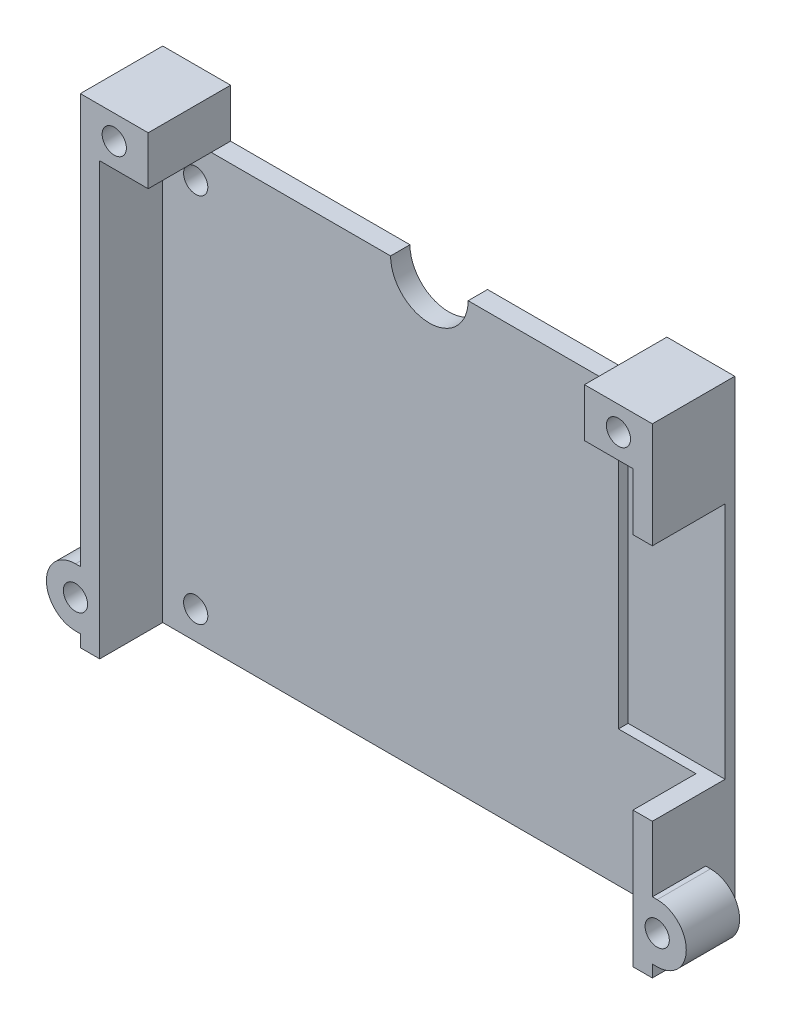
SolidWorks part; units mm, degrees
ref_plane "Front Plane" through (0, 0, 0) normal (0, 0, 1) x (1, 0, 0)
ref_plane "Top Plane" through (0, 0, 0) normal (0, 1, 0) x (1, 0, 0)
ref_plane "Right Plane" through (0, 0, 0) normal (1, 0, 0) x (0, 0, -1)
sketch "Sketch1" plane through (0, 0, 0) normal (0, 1, 0) x (1, 0, 0)
  line L0 (0, 0) -> (2, 0)
  line L1 (0, 0) -> (59, 0) construction
  line L2 (0, 0) -> (0, 8.5)
  line L3 (0, 8.5) -> (59, 8.5)
  line L4 (59, 0) -> (59, 8.5)
  line L5 (2, 0) -> (2, 6.5)
  line L6 (2, 6.5) -> (57, 6.5)
  line L7 (57, 6.5) -> (57, 0)
  line L8 (57, 0) -> (59, 0)
  dimension "D1" = 59
  dimension "D2" = 8.5
  dimension "D3" = 2
  dimension "D4" = 6.5
  dimension "D5" = 55
extrude "Boss-Extrude1" add sketch "Sketch1" along normal blind 44.5
sketch "Sketch2" plane through (59, 0, 0) normal (1, 0, 0) x (0, 0, -1)
  line L0 (0, 0) -> (0, 14) construction
  line L1 (0, 44.5) -> (0, 0) construction
  line L2 (0, 14) -> (7.5, 14)
  line L3 (7.5, 14) -> (7.5, 38.6)
  line L4 (7.5, 38.6) -> (0, 38.6)
  line L5 (0, 38.6) -> (0, 14)
  dimension "D1" = 14
  dimension "D2" = 7.5
  dimension "D3" = 24.6
extrude "Cut-Extrude1" cut sketch "Sketch2" against normal blind 10
sketch "Sketch3" plane through (0, 0, -8.5) normal (0, 0, -1) x (-1, 0, 0)
  line L0 (-59, 0) -> (-59, 7.25) construction
  line L1 (-59, 44.5) -> (-59, 0) construction
  line L2 (-59, 7.25) -> (-59, 1.25)
  line L3 (-59, 4.25) -> (-59.5, 4.25) construction
  line L4 (-59, 7.25) -> (-59.5, 7.25)
  line L5 (-59, 1.25) -> (-59.5, 1.25)
  line L6 (0, 0) -> (0, 7.25) construction
  line L7 (0, 44.5) -> (0, 0) construction
  line L8 (0, 7.25) -> (0.5, 7.25)
  line L9 (0, 7.25) -> (0, 1.25)
  line L10 (0, 1.25) -> (0.5, 1.25)
  line L11 (0, 4.25) -> (0.5, 4.25) construction
  arc A0 (-59.5, 7.25) -> (-59.5, 1.25) centre (-59.5, 4.25) ccw
  circle A1 centre (-59.5, 4.25) radius 1.25
  arc A2 (0.5, 7.25) -> (0.5, 1.25) centre (0.5, 4.25) cw
  circle A3 centre (0.5, 4.25) radius 1.25
  line M5 (0, 0) -> (0, 44.5)
  line M7 (-59, 44.5) -> (-59, 0)
  dimension "D4" = 3
  dimension "D5" = 2.5
  dimension "D11" = 3
  dimension "D12" = 2.5
  dimension "D1" = 7.25
  dimension "D2" = 6
  dimension "D3" = 0.5
  dimension "D6" = 7.25
  dimension "D7" = 0.5
  dimension "D8" = 6
  dimension "D9" = 0.5
extrude "Boss-Extrude2" add sketch "Sketch3" against normal blind 8.5 contours A1 L4 A0 L5 M7 | A3 L10 A2 L8 M5 region at (59.0695, 6.3228, -8.5) region at (-0.25, 7.1805, -8.5)
extrude "Cut-Extrude2" cut sketch "Sketch3<3>" against normal blind 11 contours L2 A1 | L9 A3 region at (58.6906, 4.25, -8.5) region at (0.3094, 4.25, -8.5)
sketch "Sketch3<3>" plane through (0, 0, -8.5) normal (0, 0, -1) x (-1, 0, 0) same geometry as "Sketch3"
sketch "Sketch4" plane through (0, 44.5, 0) normal (0, 1, 0) x (1, 0, 0)
  line L0 (59, 8.5) -> (0, 8.5) construction
  line L1 (0, 0) -> (7, 0)
  line L2 (0, 0) -> (0, 8.5)
  line L3 (0, 8.5) -> (7, 8.5)
  line L4 (7, 0) -> (7, 8.5)
  line L6 (59, 0) -> (52, 0)
  line L7 (59, 0) -> (59, 8.5)
  line L8 (59, 8.5) -> (52, 8.5)
  line L9 (52, 0) -> (52, 8.5)
  dimension "D1" = 7
  dimension "D2" = 7
extrude "Boss-Extrude3" add sketch "Sketch4" along normal blind 5
sketch "Sketch5" plane through (0, 0, -8.5) normal (0, 0, -1) x (-1, 0, 0)
  line L0 (-59, 49.5) -> (-52, 44.5) construction
  line L1 (0, 49.5) -> (-7, 44.5) construction
  circle A0 centre (-55.5, 47) radius 1.25
  circle A1 centre (-3.5, 47) radius 1.25
  dimension "D1" = 2.5
  dimension "D2" = 2.5
extrude "Cut-Extrude3" cut sketch "Sketch5" against normal through all
sketch "Sketch7" plane through (0, 0, -8.5) normal (0, 0, -1) x (-1, 0, 0)
  line L0 (-59, 0) -> (-59, 2.9) construction
  line L1 (-59, 1.25) -> (-59, 0) construction
  line L2 (-59, 2.9) -> (0, 2.9) construction
  line L3 (0, 1.25) -> (0, 0) construction
  line L4 (-53.6, 2.9) -> (-5.4, 2.9)
  line L5 (-53.6, 2.9) -> (-53.6, 41.2) construction
  line L6 (-53.6, 41.2) -> (-5.4, 41.2) construction
  circle A0 centre (-53.6, 2.9) radius 1.25
  circle A1 centre (-5.4, 2.9) radius 1.25
  circle A2 centre (-53.6, 41.2) radius 1.25
  circle A3 centre (-5.4, 41.2) radius 1.25
  point P11 (-29.5, 2.9)
  dimension "D3" = 2.5
  dimension "D4" = 2.5
  dimension "D6" = 2.5
  dimension "D8" = 2.5
  dimension "D1" = 2.9
  dimension "D2" = 48.2
  dimension "D5" = 38.3
  dimension "D7" = 48.2
extrude "Cut-Extrude4" cut sketch "Sketch7" against normal blind 10 contours A2 | A3 | A1 | A0 region at (5.4, 4.1146, -8.5) region at (54.8146, 2.9, -8.5) region at (53.6, 41.2, -8.5) region at (5.4, 41.2, -8.5)
sketch "Sketch8" plane through (0, 0, -8.5) normal (0, 0, -1) x (-1, 0, 0)
  line L0 (-52, 44.5) -> (-7, 44.5) construction
  circle A0 centre (-29.5, 44.5) radius 4
  dimension "D1" = 8
extrude "Cut-Extrude5" cut sketch "Sketch8" against normal through all
extrude "Cut-Extrude6" cut sketch "Sketch3<4>" against normal blind 3 contours A1 L4 A0 L5 M7 | A3 L10 A2 L8 M5 region at (59.0695, 6.3228, -8.5) region at (-0.25, 7.1805, -8.5)
sketch "Sketch3<4>" plane through (0, 0, -8.5) normal (0, 0, -1) x (-1, 0, 0) same geometry as "Sketch3"
extrude "Boss-Extrude4" add sketch "Sketch3<5>" against normal blind 3 contours L9 A3 | L2 A1 region at (58.6906, 4.25, -8.5) region at (0.3094, 4.25, -8.5)
sketch "Sketch3<5>" plane through (0, 0, -8.5) normal (0, 0, -1) x (-1, 0, 0) same geometry as "Sketch3"
